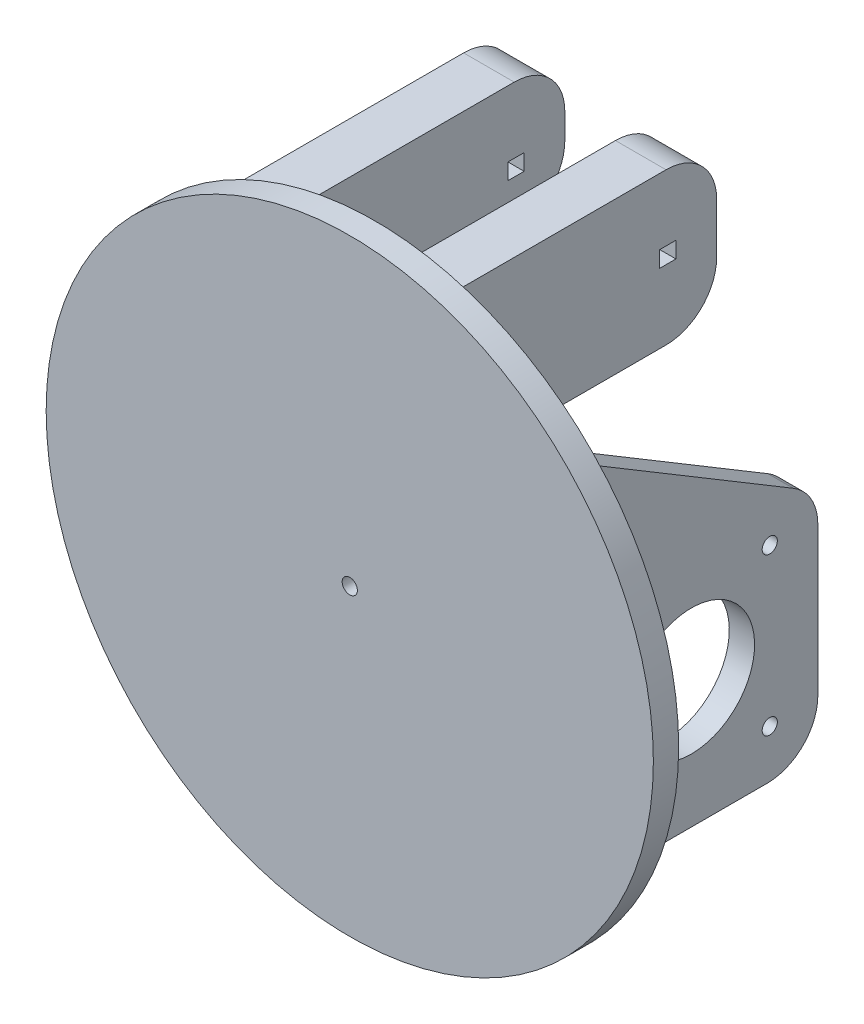
SolidWorks part; units mm, degrees
ref_plane "Front Plane" through (0, 0, 0) normal (0, 0, 1) x (1, 0, 0)
ref_plane "Top Plane" through (0, 0, 0) normal (0, 1, 0) x (1, 0, 0)
ref_plane "Right Plane" through (0, 0, 0) normal (1, 0, 0) x (0, 0, -1)
sketch "Sketch1" plane through (0, 0, 0) normal (0, 0, 1) x (1, 0, 0)
  circle A0 centre (0, 0) radius 60
  circle A1 centre (0, 0) radius 1.5
  dimension "D1" = 120
  dimension "D2" = 3
extrude "Boss-Extrude1" add sketch "Sketch1" along normal blind 5
sketch "Sketch2" plane through (0, 0, 0) normal (0, 0, -1) x (-1, 0, 0)
  line L0 (37.5, 37.5) -> (-37.5, -37.5) construction
  line L1 (-37.5, 37.5) -> (37.5, -37.5) construction
  line L3 (-37.5, 37.5) -> (-32.5, 37.5)
  line L4 (-37.5, 37.5) -> (-37.5, -37.5)
  line L5 (-37.5, -37.5) -> (-32.5, -37.5)
  line L6 (-32.5, 37.5) -> (-32.5, -37.5)
  line L7 (37.5, 37.5) -> (32.5, 37.5)
  line L8 (37.5, 37.5) -> (37.5, -37.5)
  line L9 (37.5, -37.5) -> (32.5, -37.5)
  line L10 (32.5, 37.5) -> (32.5, -37.5)
  point P7 (0, 0)
  dimension "D1" = 75
  dimension "D2" = 5
extrude "Boss-Extrude2" add sketch "Sketch2" along normal blind 50
sketch "Sketch3" plane through (32.5, 0, 0) normal (-1, 0, 0) x (0, 0, 1)
  line L0 (-50, -37.5) -> (0, 12.5) construction
  line L1 (-50, -37.5) -> (-50, 37.5) construction
  line L2 (-50, -37.5) -> (0, -37.5) construction
  line L3 (0, -37.5) -> (0, 37.5) construction
  line L4 (0, -37.5) -> (-50, 12.5) construction
  circle A0 centre (-40.5, 3) radius 1.5
  circle A1 centre (-9.5, 3) radius 1.5
  circle A2 centre (-9.5, -28) radius 1.5
  circle A3 centre (-40.5, -28) radius 1.5
  circle A4 centre (-25, -12.5) radius 12.5
  dimension "D2" = 3
  dimension "D4" = 25
  dimension "D1" = 45
  dimension "D3" = 31
extrude "Cut-Extrude1" cut sketch "Sketch3" against normal through all
sketch "Sketch6" plane through (-37.5, 0, 0) normal (-1, 0, 0) x (0, 0, 1)
  line L0 (-50, -37.5) -> (0, 12.5) construction
  line L1 (0, -37.5) -> (-50, 12.5) construction
  circle A0 centre (-40.5, 3) radius 1.5
  circle A1 centre (-9.5, 3) radius 1.5
  circle A2 centre (-9.5, -28) radius 1.5
  circle A3 centre (-40.5, -28) radius 1.5
  circle A4 centre (-25, -12.5) radius 12.5
  dimension "D1" = 3
  dimension "D3" = 25
  dimension "D2" = 31
extrude "Cut-Extrude5" cut sketch "Sketch6" against normal up to surface (5 mm away) up to face at (-32.5, 0, -25)
sketch "Sketch7" plane through (-37.5, 0, 0) normal (-1, 0, 0) x (0, 0, 1)
  line L0 (-25, -12.5) -> (-60.3553, 22.8553) construction
  line L1 (0, 60) -> (0, -60) construction
  line L2 (-50, 37.5) -> (-70, 37.5)
  line L3 (-70, 12.5) -> (-50, 12.5)
  line L4 (-50, -37.5) -> (-50, 37.5) construction
  line L5 (-70, 37.5) -> (-70, 12.5)
  line L6 (-50, 12.5) -> (-50, 37.5)
  line L7 (-58.7553, 21.2553) -> (-61.9553, 21.2553)
  line L8 (-58.7553, 21.2553) -> (-58.7553, 24.4553)
  line L9 (-58.7553, 24.4553) -> (-61.9553, 24.4553)
  line L10 (-61.9553, 21.2553) -> (-61.9553, 24.4553)
  line L11 (-58.7553, 21.2553) -> (-61.9553, 24.4553) construction
  line L12 (-58.7553, 24.4553) -> (-61.9553, 21.2553) construction
  circle A2 centre (-25, -12.5) radius 12.5 construction
  point P16 (-60.3553, 22.8553)
  dimension "D3" = 3.2
  dimension "D5" = 20
  dimension "D1" = 50
  dimension "D2" = 45
  dimension "D4" = 25
extrude "Boss-Extrude4" add sketch "Sketch7" against normal blind 5
sketch "Sketch8" plane through (-37.5, 0, 0) normal (-1, 0, 0) x (0, 0, 1)
  line L0 (-25, -12.5) -> (-25, 22.8553) construction
  line L1 (-25, 22.8553) -> (-60.3553, 22.8553) construction
  line L2 (-61.9553, 21.2553) -> (-58.7553, 24.4553) construction
  point P3 (-60.3553, 22.8553)
sketch "Sketch10" plane through (0, 0, 0) normal (0, 0, -1) x (-1, 0, 0)
  line L1 (2.5, 37.5) -> (12.5, 37.5)
  line L2 (2.5, 37.5) -> (2.5, 7.5)
  line L3 (2.5, 7.5) -> (12.5, 7.5)
  line L4 (12.5, 37.5) -> (12.5, 7.5)
  line L5 (2.5, 37.5) -> (12.5, 7.5) construction
  line L6 (2.5, 7.5) -> (12.5, 37.5) construction
  line L9 (37.5, 37.5) -> (42.5, 37.5)
  line L10 (37.5, 37.5) -> (37.5, 12.5)
  line L11 (37.5, 12.5) -> (42.5, 12.5)
  line L12 (42.5, 37.5) -> (42.5, 12.5)
  point P0 (7.5, 22.5)
  point P8 (0, 0)
  point P11 (37.5, 37.5)
  dimension "D1" = 35
  dimension "D2" = 10
  dimension "D3" = 30
  dimension "D4" = 5
  dimension "D5" = 25
extrude "Boss-Extrude5" add sketch "Sketch10" along normal blind 70
sketch "Sketch13" plane through (-32.5, 0, 0) normal (-1, 0, 0) x (0, 0, 1)
  line L1 (-61.9553, 21.2553) -> (-58.7553, 21.2553)
  line L2 (-61.9553, 21.2553) -> (-61.9553, 24.4553)
  line L3 (-61.9553, 24.4553) -> (-58.7553, 24.4553)
  line L4 (-58.7553, 21.2553) -> (-58.7553, 24.4553)
  point P4 (-59.164, 21.9561)
  point P5 (0, 0)
  point P6 (0, 0)
  point P7 (0, 0)
  point P8 (0, 0)
  point P9 (0, 0)
extrude "Cut-Extrude7" cut sketch "Sketch13" against normal through all and the other way through all
fillet "Fillet1" radius 10 4 edges at (-7.5, 37.5, -70) (-7.5, 7.5, -70) (-37.5, 12.5, -70) (-37.5, 37.5, -70)
sketch "Sketch14" plane through (0, 0, -70) normal (0, 0, -1) x (-1, 0, 0)
  line L0 (12.5, 17.5) -> (2.5, 27.5) construction
  line L1 (7.5, 22.5) -> (37.5, 22.5) construction
  line L2 (32.5, 22.5) -> (42.5, 22.5) construction
  circle A0 centre (7.5, 22.5) radius 1.5
  circle A1 centre (37.5, 22.5) radius 1.5
  point P6 (37.5, 22.5)
  point P12 (37.9595, 22.5)
  dimension "D1" = 3
extrude "Cut-Extrude8" cut sketch "Sketch14" against normal up to surface (11.2447 mm away) up to face at (-37.5, 22.8553, -58.7553)
chamfer "Chamfer1" distance 50 distance2 30 1 edges at (35, 37.5, -50) first distance on face at (35, 37.5, -25)
fillet "Fillet2" radius 10 4 edges at (35, 7.5, -50) (-35, -37.5, -50) (35, -37.5, -50) (-35, 12.5, -50)
